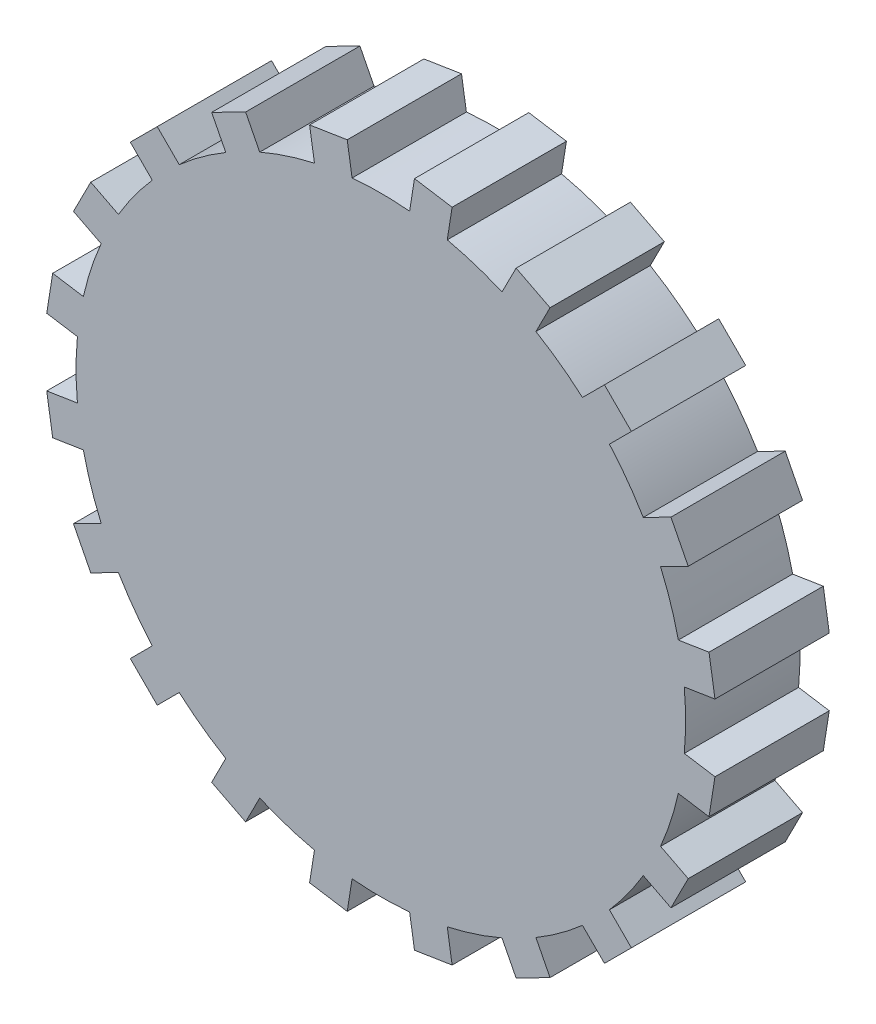
SolidWorks part; units mm, degrees
ref_plane "前视基准面" through (0, 0, 0) normal (0, 0, 1) x (1, 0, 0)
ref_plane "上视基准面" through (0, 0, 0) normal (0, 1, 0) x (1, 0, 0)
ref_plane "右视基准面" through (0, 0, 0) normal (1, 0, 0) x (0, 0, -1)
other "Configuration Table"
sketch "草图1" plane through (0, 0, 0) normal (0, 0, 1) x (1, 0, 0)
  circle A0 centre (0, 0) radius 40
extrude "凸台-拉伸1" add sketch "草图1" along normal blind 15
sketch "草图2" plane through (0, 0, 0) normal (0, 0, 1) x (1, 0, 0)
  line L0 (39.4048, 3.7099) -> (43.8494, 4.4139)
  line L1 (43.8494, 4.4139) -> (43.0672, 9.3523)
  line L2 (43.0672, 9.3523) -> (38.6226, 8.6484)
  line L3 (38.6226, 8.6484) -> (39.4048, 3.7099)
extrude "凸台-拉伸2" add sketch "草图2" along normal blind 15
ref_axis "基准轴1" through (0, 0, 15) along (0, 0, -1)
pattern_circular "阵列(圆周)1" count 20 over 360 about axis through (0, 0, 15) along (0, 0, -1) of "凸台-拉伸2"
